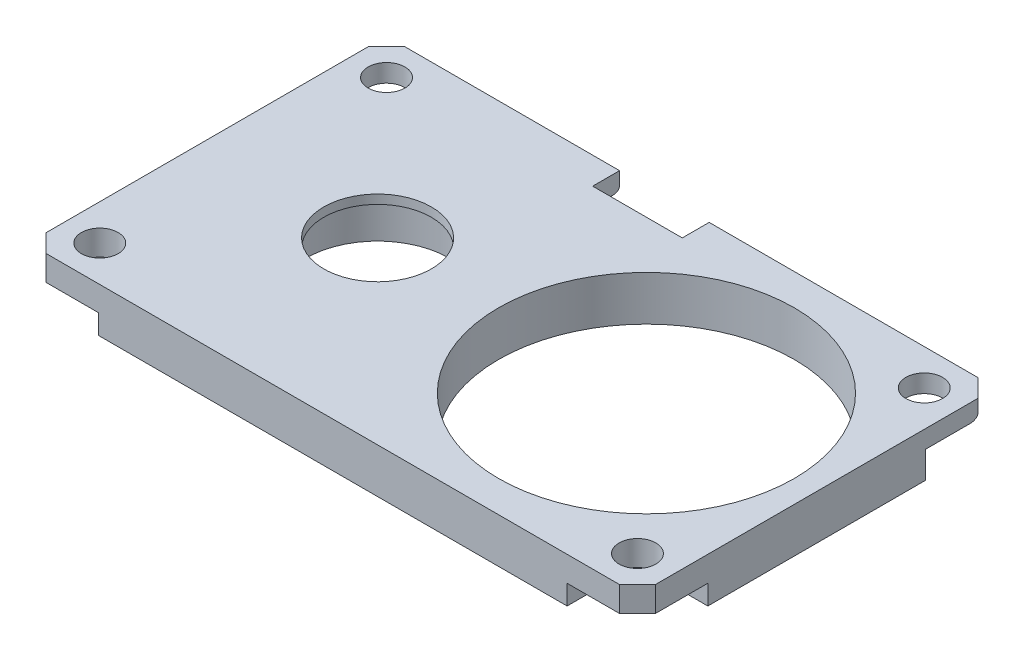
SolidWorks part; units mm, degrees
material "Tough 2000"
ref_plane "Front Plane" through (0, 0, 0) normal (0, 0, 1) x (1, 0, 0)
ref_plane "Top Plane" through (0, 0, 0) normal (0, 1, 0) x (1, 0, 0)
ref_plane "Right Plane" through (0, 0, 0) normal (1, 0, 0) x (0, 0, -1)
sketch "Sketch1" plane through (0, 0, 0) normal (0, 1, 0) x (1, 0, 0)
  line L1 (-17, 10) -> (17, 10)
  line L2 (-17, 10) -> (-17, -10)
  line L3 (-17, -10) -> (17, -10)
  line L4 (17, 10) -> (17, -10)
  line L5 (-17, 10) -> (17, -10) construction
  line L6 (-17, -10) -> (17, 10) construction
  point P0 (0, 0)
  dimension "D1" = 34
  dimension "D2" = 20
extrude "Boss-Extrude1" add sketch "Sketch1" along normal blind 2.5
sketch "Sketch2" plane through (0, 2.5, 0) normal (0, 1, 0) x (1, 0, 0)
  line L0 (-7.5, 0) -> (0, 0) construction
  line L1 (0, 0) -> (7.5, 0) construction
  circle A0 centre (-7.5, 0) radius 3
  circle A1 centre (7.5, 0) radius 8.25
  dimension "D1" = 7.5
  dimension "D2" = 6
  dimension "D3" = 16.5
extrude "Cut-Extrude1" cut sketch "Sketch2" against normal blind 5
sketch "Sketch5" plane through (0, 2.5, 0) normal (0, 1, 0) x (1, 0, 0)
  circle A0 centre (-7.5, 0) radius 4.025
  dimension "D1" = 8.05
extrude "Cut-Extrude4" cut sketch "Sketch5" against normal blind 2
sketch "Sketch3" plane through (0, 2.5, 0) normal (0, 1, 0) x (1, 0, 0)
  line L0 (0, 10) -> (0, 0) construction
  line L1 (17, 10) -> (-17, 10) construction
  line L2 (0, 0) -> (17, 0) construction
  line L3 (17, -10) -> (17, 10) construction
  circle A0 centre (15, 8) radius 1.025
  circle A1 centre (-15, 8) radius 1.025
  circle A2 centre (-15, -8) radius 1.025
  circle A3 centre (15, -8) radius 1.025
  dimension "D1" = 30
  dimension "D2" = 16
  dimension "D3" = 2.05
extrude "Cut-Extrude2" cut sketch "Sketch3" against normal blind 4
sketch "Sketch4" plane through (0, 2.5, 0) normal (0, 1, 0) x (1, 0, 0)
  circle A0 centre (-15, 8) radius 1.925
  circle A1 centre (-15, -8) radius 1.925
  circle A2 centre (15, 8) radius 1.925
  circle A3 centre (15, -8) radius 1.925
  dimension "D1" = 3.85
extrude "Cut-Extrude3" cut sketch "Sketch4" against normal blind 1.5
sketch "Sketch6" plane through (0, 2.5, 0) normal (0, 1, 0) x (1, 0, 0)
  line L14 (0, 0) -> (0, 10) construction
  line L15 (17, 10) -> (-17, 10) construction
  line L16 (17, 10) -> (-17, 10)
  line L17 (-15, 6.075) -> (-17, 6.075)
  line L19 (-17, 10) -> (-17, -10) construction
  line L20 (-17, 6.075) -> (-17, 10)
  line L22 (13.1411, 8.5) -> (-13.1411, 8.5)
  line L23 (17, 6.075) -> (17, 10)
  line L24 (15, 6.075) -> (17, 6.075)
  circle A1 centre (-15, 8) radius 1.925 construction
  arc A3 (-15, 6.075) -> (-13.1411, 8.5) centre (-15, 8) ccw
  arc A5 (15, 6.075) -> (13.1411, 8.5) centre (15, 8) cw
  point P20 (0, 8.5)
  dimension "D1" = 1.5
extrude "Cut-Extrude5" cut sketch "Sketch6" against normal blind 1.5
fillet "Fillet1" radius 2 2 edges at (-13.1411, 1.75, -8.5) (13.1411, 1.75, -8.5)
chamfer "Chamfer1" distance 1 angle 45 4 edges at (17, 1.25, 10) (-17, 1.25, 10) (-17, 0.5, -10) (17, 0.5, -10)
fillet "Fillet2" radius 0.3 3 edges at (-16.5, 1, -9.5) (16.5, 1, -9.5) (0, 1, -10)
mirror "Mirror1" about plane through (0, 0, 0) normal (0, 1, 0) of "Fillet2", "Chamfer1", "Fillet1", "Cut-Extrude5", "Cut-Extrude3", "Cut-Extrude2", "Cut-Extrude4", "Cut-Extrude1", "Boss-Extrude1"
sketch "Sketch7" plane through (0, 0, 10) normal (0, 0, 1) x (1, 0, 0)
  line L1 (-17, 2.5) -> (17, 2.5)
  line L2 (-17, 2.5) -> (-17, 0)
  line L3 (-17, 0) -> (17, 0)
  line L4 (17, 2.5) -> (17, 0)
extrude "Cut-Extrude6" cut sketch "Sketch7" against normal blind 50
sketch "Sketch8" plane through (0, -1, 0) normal (0, -1, 0) x (1, 0, 0)
  line L0 (-11.3729, -8.5) -> (11.3729, -8.5) construction
  line L1 (-4, -8.5) -> (1, -8.5)
  line L2 (-4, -8.5) -> (-4, -10)
  line L3 (-4, -10) -> (1, -10)
  line L4 (1, -8.5) -> (1, -10)
  line L5 (16, -10) -> (-16, -10) construction
  point P8 (-1.5, -8.5)
  dimension "D1" = 5
  dimension "D2" = 1.5
extrude "Cut-Extrude7" cut sketch "Sketch8" against normal blind 50
sketch "Sketch9" plane through (0, -2.5, 0) normal (0, -1, 0) x (1, 0, 0)
  circle A0 centre (-7.5, 0) radius 4.025
  circle A1 centre (-7.5, 0) radius 5.525
  circle A2 centre (-7.5, 0) radius 4.025 construction
  dimension "D1" = 1.5
extrude "Boss-Extrude2" add sketch "Sketch9" along normal blind 0.5
sketch "Sketch10" plane through (0, -2.5, 0) normal (0, -1, 0) x (1, 0, 0)
  line L0 (-15, 6.075) -> (-17, 6.075)
  line L1 (-17, -6.075) -> (-17, 9) construction
  line L2 (-17, 6.075) -> (-17, 9)
  line L3 (-17, 9) -> (-16, 10)
  line L4 (-16, 10) -> (-13.075, 10)
  line L5 (-16, 10) -> (16, 10) construction
  line L6 (-13.075, 10) -> (-13.075, 8)
  line L7 (0, 0) -> (0, 10) construction
  line L8 (13.075, 10) -> (13.075, 8)
  line L9 (16, 10) -> (13.075, 10)
  line L10 (17, 9) -> (16, 10)
  line L11 (17, 6.075) -> (17, 9)
  line L12 (15, 6.075) -> (17, 6.075)
  circle A0 centre (-15, 8) radius 1.925 construction
  arc A1 (-13.075, 8) -> (-15, 6.075) centre (-15, 8) ccw
  arc A2 (13.075, 8) -> (15, 6.075) centre (15, 8) cw
extrude "Cut-Extrude8" cut sketch "Sketch10" against normal up to surface (1.5 mm away) up to face at (-15, -1, 9.925)
sketch "Sketch11" plane through (0, -1, 0) normal (0, -1, 0) x (1, 0, 0)
  line L5 (15, 6.075) -> (17, 6.075)
  line L6 (17, 6.075) -> (17, 9)
  line L7 (17, 9) -> (16, 10)
  line L8 (16, 10) -> (13.075, 10)
  line L9 (13.075, 10) -> (13.075, 8)
  line L10 (-13.075, 8) -> (-13.075, 10)
  line L11 (-13.075, 10) -> (-16, 10)
  line L12 (-16, 10) -> (-17, 9)
  line L13 (-17, 9) -> (-17, 6.075)
  line L14 (-17, 6.075) -> (-15, 6.075)
  line L15 (-13.075, 8) -> (-13.075, 10)
  line L16 (-13.075, 10) -> (-16, 10)
  line L17 (-16, 10) -> (-17, 9)
  line L18 (-17, 9) -> (-17, 6.075)
  line L19 (-17, 6.075) -> (-15, 6.075)
  line L20 (15, 6.075) -> (17, 6.075)
  line L21 (17, 6.075) -> (17, 9)
  line L22 (17, 9) -> (16, 10)
  line L23 (16, 10) -> (13.075, 10)
  line L24 (13.075, 10) -> (13.075, 8)
  circle A1 centre (-15, 8) radius 1.025 construction
  arc A2 (-15, 6.075) -> (-13.075, 8) centre (-15, 8) ccw
  arc A3 (-15, 6.075) -> (-13.075, 8) centre (-15, 8) ccw
  circle A4 centre (15, 8) radius 1.025
  circle A5 centre (15, 8) radius 1.025
  circle A6 centre (-15, 8) radius 1.025
  arc A7 (13.075, 8) -> (15, 6.075) centre (15, 8) ccw
  arc A8 (13.075, 8) -> (15, 6.075) centre (15, 8) ccw
  dimension "D1" = 0
  dimension "D2" = 0
  dimension "D3" = 0
extrude "Boss-Extrude3" add sketch "Sketch11" along normal blind 0.4
